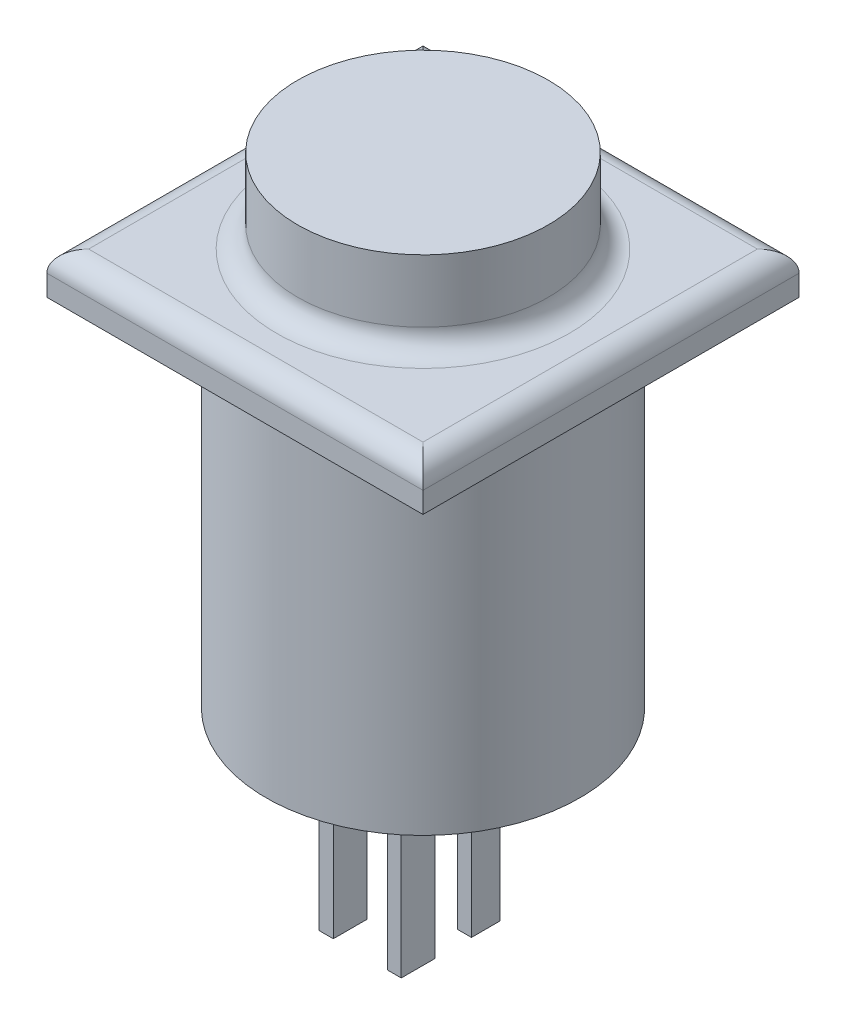
SolidWorks part; units mm, degrees
ref_plane "Ön Düzlem" through (0, 0, 0) normal (0, 0, 1) x (1, 0, 0)
ref_plane "Üst Düzlem" through (0, 0, 0) normal (0, 1, 0) x (1, 0, 0)
ref_plane "Sağ Düzlem" through (0, 0, 0) normal (1, 0, 0) x (0, 0, -1)
sketch "Çizim1" plane through (0, 0, 0) normal (0, 1, 0) x (1, 0, 0)
  circle A0 centre (0, 0) radius 6
  dimension "D1" = 12
extrude "Yükseklik-Ekstrüzyon1" add sketch "Çizim1" along normal blind 4
sketch "Çizim2" plane through (0, 0, 0) normal (0, -1, 0) x (1, 0, 0)
  line L1 (-9, 9) -> (9, 9)
  line L2 (-9, 9) -> (-9, -9)
  line L3 (-9, -9) -> (9, -9)
  line L4 (9, 9) -> (9, -9)
  line L5 (-9, 9) -> (9, -9) construction
  line L6 (-9, -9) -> (9, 9) construction
  point P0 (0, 0)
  dimension "D1" = 18
  dimension "D2" = 18
extrude "Yükseklik-Ekstrüzyon2" add sketch "Çizim2" along normal blind 2
fillet "Radyus1" radius 1 5 edges at (0, 0, 9) (-9, 0, 0) (0, 0, -9) (9, 0, 0) (0, 0, -6)
sketch "Çizim3" plane through (0, -2, 0) normal (0, -1, 0) x (1, 0, 0)
  circle A0 centre (0, 0) radius 7.5
extrude "Yükseklik-Ekstrüzyon3" add sketch "Çizim3" along normal blind 17
sketch "Çizim4" plane through (0, -19, 0) normal (0, -1, 0) x (1, 0, 0)
  line L1 (3.0316, 4.73) -> (3.6891, 4.73)
  line L2 (3.0316, 4.73) -> (3.0316, 3.1229)
  line L3 (3.0316, 3.1229) -> (3.6891, 3.1229)
  line L4 (3.6891, 4.73) -> (3.6891, 3.1229)
  line L5 (-0.2557, 4.73) -> (0.4383, 4.73)
  line L6 (-0.2557, 4.73) -> (-0.2557, 3.1229)
  line L7 (-0.2557, 3.1229) -> (0.4383, 3.1229)
  line L8 (0.4383, 4.73) -> (0.4383, 3.1229)
  line L9 (3.0316, 1.3697) -> (3.6891, 1.3697)
  line L10 (3.0316, 1.3697) -> (3.0316, 0)
  line L11 (3.0316, 0) -> (3.6891, 0)
  line L12 (3.6891, 1.3697) -> (3.6891, 0)
  line L13 (-0.2557, 1.3697) -> (0.4383, 1.3697)
  line L14 (-0.2557, 1.3697) -> (-0.2557, 0)
  line L15 (-0.2557, 0) -> (0.4383, 0)
  line L16 (0.4383, 1.3697) -> (0.4383, 0)
extrude "Yükseklik-Ekstrüzyon4" add sketch "Çizim4" along normal blind 7
